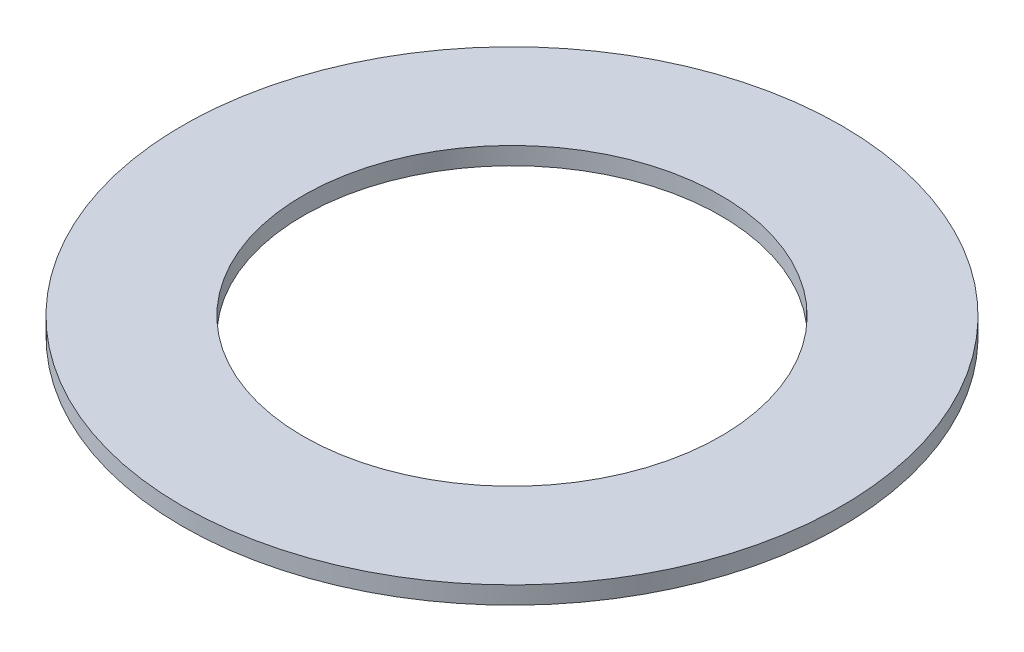
SolidWorks part; units mm, degrees
ref_plane "Front Plane" through (0, 0, 0) normal (0, 0, 1) x (1, 0, 0)
ref_plane "Top Plane" through (0, 0, 0) normal (0, 1, 0) x (1, 0, 0)
ref_plane "Right Plane" through (0, 0, 0) normal (1, 0, 0) x (0, 0, -1)
sketch "Sketch1" plane through (0, 0, 0) normal (0, 1, 0) x (1, 0, 0)
  circle A0 centre (0, 0) radius 75
  dimension "FLANGE_OD" = 150
extrude "Boss-Extrude1" add sketch "Sketch1" along normal blind 4
sketch "Sketch2" plane through (0, 0, 0) normal (0, 1, 0) x (1, 0, 0)
  circle A0 centre (0, 0) radius 47.5
  dimension "BORE_D" = 95
extrude "Cut-Extrude1" cut sketch "Sketch2" along normal through all
sketch "Sketch3" plane through (0, 4, 0) normal (0, 1, 0) x (1, 0, 0)
  circle A0 centre (0, 0) radius 32.6632 construction
  circle A1 centre (-32.6632, 0) radius 1.5124
  dimension "BOLT_D" = 3.0249
  dimension "BOLT_PCD" = 65.3264
extrude "Cut-Extrude2" cut sketch "Sketch3" against normal blind 3.3696 rebuild error yes
pattern_circular "CirPattern1" count 6 over 360 rebuild error yes
